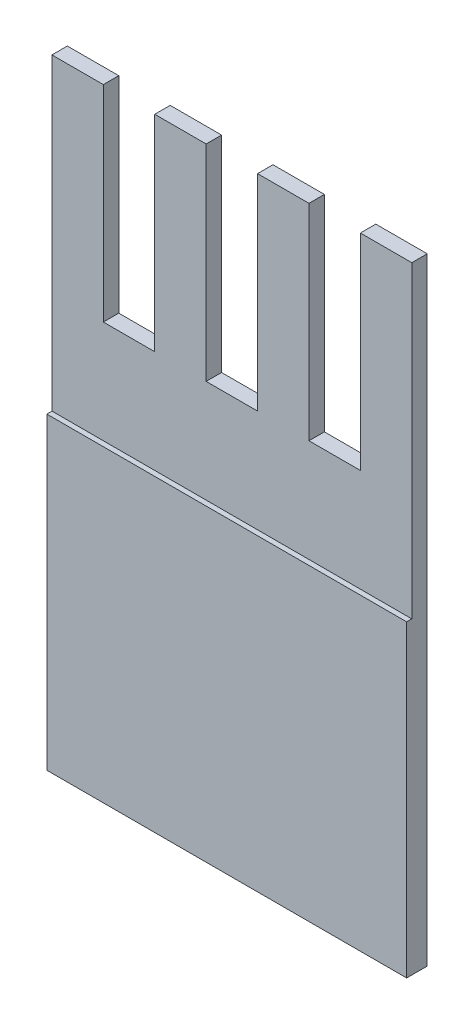
SolidWorks part; units mm, degrees
ref_plane "Front" through (0, 0, 0) normal (0, 0, 1) x (1, 0, 0)
ref_plane "Top" through (0, 0, 0) normal (0, 1, 0) x (1, 0, 0)
ref_plane "Side" through (0, 0, 0) normal (1, 0, 0) x (0, 0, -1)
sketch "Sketch1" plane through (0, 0, 0) normal (0, 0, 1) x (1, 0, 0)
  line L0 (-12.5, 30) -> (-17.5, 30)
  line L1 (17.5, 30) -> (12.5, 30)
  line L2 (17.5, 30) -> (17.5, -30)
  line L3 (17.5, -30) -> (-17.5, -30)
  line L4 (-17.5, 30) -> (-17.5, -30)
  line L5 (-2.5, 10) -> (2.5, 10)
  line L6 (-12.5, 10) -> (-7.5, 10)
  line L7 (-17.5, 30) -> (-12.5, 30)
  line L8 (-17.5, 30) -> (-17.5, 10)
  line L9 (-12.5, 10) -> (-7.5, 10)
  line L10 (17.5, 30) -> (17.5, 10)
  line L20 (-2.5, 30) -> (-2.5, 10)
  line L21 (-2.5, 10) -> (2.5, 10)
  line L22 (2.5, 30) -> (2.5, 10)
  line L24 (-7.5, 30) -> (-7.5, 10)
  line L25 (-7.5, 10) -> (-12.5, 10)
  line L26 (-12.5, 30) -> (-12.5, 10)
  line L28 (7.5, 30) -> (7.5, 10)
  line L29 (7.5, 10) -> (12.5, 10)
  line L30 (12.5, 30) -> (12.5, 10)
  line L31 (-7.5, 30) -> (-2.5, 30)
  line L32 (-17.5, 10) -> (-17.5, 0)
  line L33 (-2.5, 30) -> (-7.5, 30)
  line L34 (2.5, 30) -> (7.5, 30)
  line L35 (7.5, 30) -> (2.5, 30)
  line L36 (12.5, 30) -> (17.5, 30)
  line L37 (-17.5, 0) -> (17.5, 0)
  line L38 (17.5, 10) -> (17.5, 0)
  line L39 (-2.5, 10) -> (2.5, 10)
  line L40 (7.5, 10) -> (12.5, 10)
  line L41 (7.5, 10) -> (12.5, 10)
  point P0 (0, 0)
extrude "Boss-Extrude5" add sketch "Sketch1" along normal blind 2 contours L37 L4 L3 L2 region at (0, -15, 0)
extrude "Boss-Extrude6" add sketch "Sketch1<7>" along normal blind 1.5 contours L4 L37 L2 L1 L30 L29 L28 L34 L22 L5 L20 L31 L24 L6 L26 L0 region at (-12.961, 20, 0)
sketch "Sketch1<7>" plane through (0, 0, 0) normal (0, 0, 1) x (1, 0, 0) same geometry as "Sketch1"
